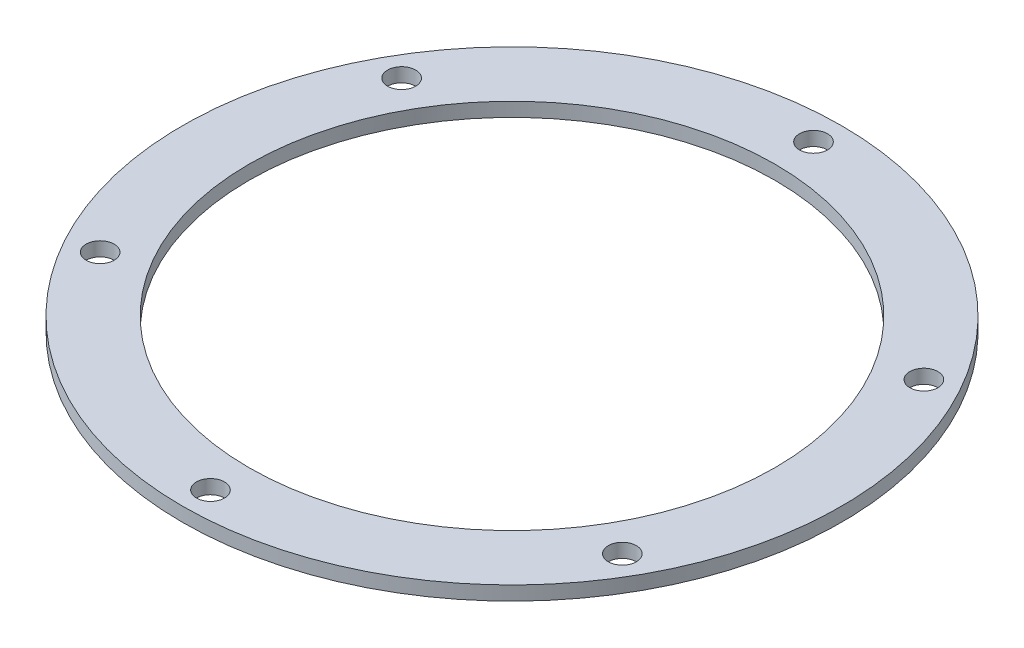
SolidWorks part; units mm, degrees
material "PLA"
ref_plane "Front Plane" through (0, 0, 0) normal (0, 0, 1) x (1, 0, 0)
ref_plane "Top Plane" through (0, 0, 0) normal (0, 1, 0) x (1, 0, 0)
ref_plane "Right Plane" through (0, 0, 0) normal (1, 0, 0) x (0, 0, -1)
sketch "Sketch1" plane through (0, 0, 0) normal (0, 1, 0) x (1, 0, 0)
  circle A0 centre (0, 0) radius 47
  circle A1 centre (0, 0) radius 37.5
  circle A2 centre (0, 0) radius 43 construction
  circle A3 centre (0, 43) radius 2
  circle A4 centre (37.2391, 21.5) radius 2
  circle A5 centre (37.2391, -21.5) radius 2
  circle A6 centre (0, -43) radius 2
  circle A7 centre (-37.2391, -21.5) radius 2
  circle A8 centre (-37.2391, 21.5) radius 2
  point P19 (0, 0)
  dimension "D1" = 94
  dimension "D2" = 75
  dimension "D3" = 86
  dimension "D4" = 4
  dimension "D5" = 6
extrude "Boss-Extrude1" add sketch "Sketch1" along normal blind 2
equation "\"Np_b\" = 48"
equation "\"Np_s\" = 28"
equation "\"Nr_b\" = 152"
equation "\"Nr_s\" = 132"
equation "\"Ns\" = 56"
equation "\"Motor_case_ID\" = 96.8"
equation "\"Motor_case_OD_base_to_chamfer\" = 5"
equation "\"Motor_case_OD_max\" = 111.3"
equation "\"Motor_case_thickness\" = 2.5"
equation "\"air_flow_hole_offset\" = 3"
equation "\"standard_bearing_insertion_chamfer\" = 0.5"
equation "\"alpha_p_b\" = 0.8539582918412414"
equation "\"alpha_p_s\" = 0.8539582918412485"
equation "\"alpha_r_b\" = 0.8539582918412236"
equation "\"alpha_r_s\" = 0.8539582918412449"
equation "\"alpha_s\" = 0.8539582918412485"
equation "\"base_plate_thickness\" = 4"
equation "\"bearing_ID\" = 60"
equation "\"bearing_OD\" = 78"
equation "\"bearing_height\" = 10"
equation "\"bearing mount thickness\" = 8"
equation "\"bearing_retainer_thickness\" = 2"
equation "\"beta_p_b\" = 2.042083416317517"
equation "\"beta_p_s\" = 4.720654844888932"
equation "\"beta_r_b\" = 2.8921271099982366"
equation "\"beta_r_s\" = 3.071552947318853"
equation "\"beta_s\" = 1.5063691306032174"
equation "\"carrier_PCD\" = 52.0"
equation "\"carrier_bearing_step_width\" = 1.5"
equation "\"carrier_small_ring_inner_bearing_ID\" = 20"
equation "\"carrier_small_ring_inner_bearing_OD\" = 32"
equation "\"carrier_small_ring_inner_bearing_flap\" = 2"
equation "\"carrier_small_ring_inner_bearing_height\" = 7"
equation "\"carrier_thickness\" = 4"
equation "\"carrier_trapezoidal_support_hole_PCD_offset_bearing_ID\" = 4"
equation "\"carrier_trapezoidal_support_hole_dia\" = 3"
equation "\"carrier_trapezoidal_support_hole_socket_head_dia\" = 5.5"
equation "\"carrier_trapezoidal_support_hole_wrench_size\" = 5.5"
equation "\"carrier_trapezoidal_support_sun_offset\" = 5"
equation "\"case_dist\" = 6.5"
equation "\"case_mounting_PCD\" = 103.8"
equation "\"case_mounting_bolt_depth\" = 4.5"
equation "\"case_mounting_hole_allen_socket_dia\" = 5.5"
equation "\"case_mounting_hole_dia\" = 3"
equation "\"case_mounting_hole_shift\" = 1.0"
equation "\"case_mounting_nut_clearance\" = 2"
equation "\"case_mounting_nut_thickness\" = 2.4"
equation "\"case_mounting_surface_height\" = 4"
equation "\"case_mounting_wrench_size\" = 5.5"
equation "\"central_hole_offset_from_motor_mount_PCD\" = 5"
equation "\"clearance_case_mount_holes_shell_thickness\" = 1"
equation "\"clearance_motor_and_case\" = 5"
equation "\"clearance_planet\" = 1.5"
equation "\"clearance_sun_coupler_sec_carrier\" = 1.5"
equation "\"clr_tip_root\" = 0.125"
equation "\"clr_tip_root_s\" = 0.125"
equation "\"db_p_b\" = 22.552622898861802"
equation "\"db_p_s\" = 13.155696691002717"
equation "\"db_r_b\" = 71.41663917972905"
equation "\"db_r_s\" = 62.01971297186996"
equation "\"db_s\" = 26.311393382005434"
equation "\"dp_p_b\" = 24.0"
equation "\"dp_p_s\" = 14.0"
equation "\"dp_r_b\" = 76.0"
equation "\"dp_r_s\" = 66.0"
equation "\"dp_s\" = 28.0"
equation "\"driver_lower_holes_dist_from_center\" = 13"
equation "\"driver_mount_height\" = 6"
equation "\"driver_mount_holes_dia\" = 3"
equation "\"driver_mount_inserts_OD\" = 4.8"
equation "\"driver_mount_thickness\" = 1.5"
equation "\"driver_side_holes_dist_from_center\" = 22.5"
equation "\"driver_upper_holes_dist_from_center\" = 29"
equation "\"fw_p_b\" = 9.918018611286483"
equation "\"fw_p_s\" = 15.90536252346366"
equation "\"fw_r_b\" = 9.918018611286483"
equation "\"fw_r_s\" = 14.40536252346366"
equation "\"fw_s_calc\" = 2.7970255760332914"
equation "\"fw_s_used\" = 33.32338113475014"
equation "\"gear_casing_big_ring_to_bearing_dist\" = 24.90536252346366"
equation "\"gear_casing_thickness\" = 4"
equation "\"h_a\" = 0.5"
equation "\"h_b\" = 0.625"
equation "\"h_f\" = 0.625"
equation "\"module\" = 0.5"
equation "\"motor_OD\" = 86.8"
equation "\"motor_case_OD_base\" = 101.8"
equation "\"motor_height\" = 26.5"
equation "\"motor_mount_hole_PCD\" = 32"
equation "\"motor_mount_hole_dia\" = 4"
equation "\"motor_mount_hole_num\" = 4"
equation "\"motor_output_hole_CSK_OD\" = 8"
equation "\"motor_output_hole_CSK_head_height\" = 2.0"
equation "\"motor_output_hole_PCD\" = 23"
equation "\"motor_output_hole_dia\" = 4"
equation "\"motor_output_hole_num\" = 4"
equation "\"num_planet\" = 4"
equation "\"output_mounting_PCD\" = 86"
equation "\"output_mounting_hole_dia\" = 4"
equation "\"output_mounting_nut_depth\" = 3"
equation "\"output_mounting_nut_thickness\" = 3.2"
equation "\"output_mounting_nut_wrench_size\" = 7"
equation "\"pattern_bulge_dia\" = 3"
equation "\"pattern_depth\" = 2"
equation "\"pattern_num_bulge\" = 18"
equation "\"pattern_offset_from_motor_case_OD_base\" = 3"
equation "\"planet_bearing_OD\" = 12"
equation "\"planet_bearing_width\" = 3.5"
equation "\"planet_bore\" = 10"
equation "\"planet_pin_bolt_dia\" = 5"
equation "\"planet_pin_bolt_wrench_size\" = 8"
equation "\"planet_pin_socket_head_dia\" = 8.5"
equation "\"planet_shaft_dia\" = 8"
equation "\"planet_shaft_step_offset\" = 1"
equation "\"pressure_angle\" = 20.0"
equation "\"pressure angle\" = 20.0"
equation "\"ring_OD_b\" = 86.0"
equation "\"ring_radial_thickness\" = 5"
equation "\"ring_to_chamfer_clearance\" = 1.5"
equation "\"sec_carrier_thickness\" = 5"
equation "\"small_ring_case_thickness\" = 4"
equation "\"small_ring_output_wall_thickness\" = 5"
equation "\"small_ring_output_wall_to_bearing_shaft_attachement_hole_CSK_OD\" = 8"
equation "\"small_ring_output_wall_to_bearing_shaft_attachement_hole_CSK_head_height\" = 2.0"
equation "\"small_ring_output_wall_to_bearing_shaft_attachement_hole_depth\" = 6.5"
equation "\"small_ring_output_wall_to_bearing_shaft_attachement_hole_dia\" = 4"
equation "\"small_ring_output_wall_to_bearing_shaft_attachement_hole_num\" = 3"
equation "\"small_ring_output_wall_to_bearing_shaft_attachement_hole_pcd\" = 12"
equation "\"small_ring_output_wall_to_bearing_shaft_attachement_nut_thickness\" = 3.2"
equation "\"small_ring_output_wall_to_bearing_shaft_attachement_nut_wrench\" = 7"
equation "\"standard_clearance_1_5mm\" = 1.5"
equation "\"standard_fillet_1_5mm\" = 1.5"
equation "\"sun_central_bolt_dia\" = 5"
equation "\"sun_central_bolt_socket_head_dia\" = 8.5"
equation "\"sun_coupler_hub_thickness\" = 4"
equation "\"sun_hub_dia\" = 30.0"
equation "\"sun_shaft_bearing_ID\" = 8"
equation "\"sun_shaft_bearing_OD\" = 16"
equation "\"sun_shaft_bearing_width\" = 5"
equation "\"wire_slot_dist_from_center\" = 38"
equation "\"wire_slot_length\" = 10"
equation "\"wire_slot_radius\" = 2.5"
equation "\"tight_clearance_3DP\"= 0.4"
equation "\"loose_clearance_3DP\"= 0.8"
equation "\"D1@Sketch1\"= \"bearing_OD\" + \"bearing mount thickness\" * 2"
equation "\"D2@Sketch1\"=\"bearing_OD\" -  \"standard_clearance_1_5mm\"*2"
equation "\"D3@Sketch1\"= \"output_mounting_PCD\""
equation "\"D4@Sketch1\"= \"output_mounting_hole_dia\""
equation "\"D1@Boss-Extrude1\"= \"bearing_retainer_thickness\""
